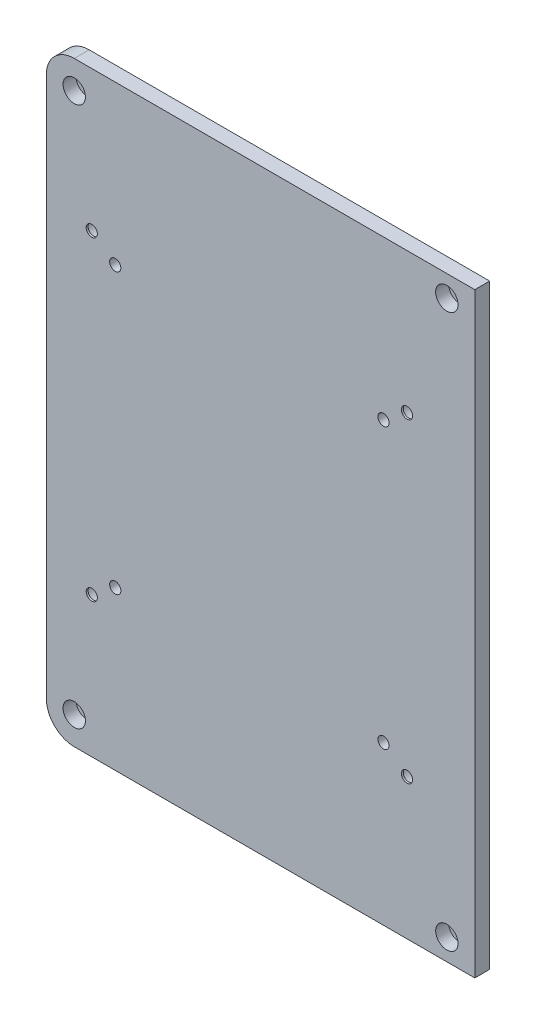
SolidWorks part; units mm, degrees
ref_plane "Front Plane" through (0, 0, 0) normal (0, 0, 1) x (1, 0, 0)
ref_plane "Top Plane" through (0, 0, 0) normal (0, 1, 0) x (1, 0, 0)
ref_plane "Right Plane" through (0, 0, 0) normal (1, 0, 0) x (0, 0, -1)
sketch "Sketch1" plane through (0, 0, 0) normal (0, 0, 1) x (1, 0, 0)
  line L1 (-107.5, 80) -> (107.5, 80)
  line L2 (-115, 72.5) -> (-115, -72.5)
  line L3 (-107.5, -80) -> (107.5, -80)
  line L4 (115, 72.5) -> (115, -72.5)
  line L5 (-115, 80) -> (115, -80) construction
  line L6 (-115, -80) -> (115, 80) construction
  arc A0 (-115, -72.5) -> (-107.5, -80) centre (-107.5, -72.5) ccw
  arc A1 (107.5, -80) -> (115, -72.5) centre (107.5, -72.5) ccw
  arc A2 (107.5, 80) -> (115, 72.5) centre (107.5, 72.5) cw
  arc A3 (-107.5, 80) -> (-115, 72.5) centre (-107.5, 72.5) ccw
  point P0 (0, 0)
  dimension "D3" = 7.5
  dimension "D1" = 230
  dimension "D2" = 160
extrude "Boss-Extrude1" add sketch "Sketch1" along normal blind 4
sketch "Sketch2" plane through (0, 0, 4) normal (0, 0, 1) x (1, 0, 0)
  line L0 (-115, 72.5) -> (-115, -72.5) construction
  line L1 (-107.5, -80) -> (107.5, -80) construction
  line L2 (107.5, 80) -> (-107.5, 80) construction
  line L3 (115, -72.5) -> (115, 72.5) construction
  circle A0 centre (-107.5, -72.5) radius 1.75
  circle A1 centre (-107.5, 72.5) radius 1.75
  circle A2 centre (107.5, -72.5) radius 1.75
  circle A3 centre (107.5, 72.5) radius 1.75
  dimension "D1" = 7.5
  dimension "D3" = 3.5
  dimension "D4" = 3.5
  dimension "D7" = 3.5
  dimension "D10" = 3.5
  dimension "D2" = 7.5
  dimension "D5" = 7.5
  dimension "D6" = 7.5
  dimension "D8" = 7.5
  dimension "D9" = 7.5
  dimension "D11" = 7.5
  dimension "D12" = 7.5
extrude "Cut-Extrude1" cut sketch "Sketch2" against normal blind 10
sketch "Sketch3" plane through (0, 0, 4) normal (0, 0, 1) x (1, 0, 0)
  circle A0 centre (-107.5, -72.5) radius 3
  circle A1 centre (-107.5, 72.5) radius 3
  circle A2 centre (107.5, 72.5) radius 3
  circle A3 centre (107.5, -72.5) radius 3
  dimension "D1" = 6
  dimension "D2" = 6
  dimension "D3" = 6
  dimension "D4" = 6
extrude "Cut-Extrude2" cut sketch "Sketch3" against normal blind 3.5
sketch "Sketch4" plane through (0, 0, 4) normal (0, 0, 1) x (1, 0, 0)
  line L0 (107.5, 80) -> (-107.5, 80) construction
  line L3 (-115, 72.5) -> (-115, -72.5) construction
  line L4 (-107.5, -80) -> (107.5, -80) construction
  circle A0 centre (-96.5, 37.5) radius 1.5
  circle A1 centre (-96.5, -37.5) radius 1.5
  circle A2 centre (-24.5, 37.5) radius 1.5
  circle A3 centre (-24.5, -37.5) radius 1.5
  dimension "D2" = 3
  dimension "D3" = 3
  dimension "D6" = 3
  dimension "D7" = 3
  dimension "D1" = 75
  dimension "D4" = 42.5
  dimension "D5" = 18.5
  dimension "D8" = 72
  dimension "D9" = 72
  dimension "D10" = 42.5
  dimension "D11" = 42.5
extrude "Cut-Extrude3" cut sketch "Sketch4" against normal through all
sketch "Sketch5" plane through (0, 0, 4) normal (0, 0, 1) x (1, 0, 0)
  line L0 (-107.5, -80) -> (107.5, -80) construction
  line L2 (115, -72.5) -> (115, 72.5) construction
  circle A0 centre (95, -62.5) radius 1.375
  circle A1 centre (95, 62.5) radius 1.375
  circle A2 centre (41.7, -62.5) radius 1.375
  circle A3 centre (41.7, 62.5) radius 1.375
  dimension "D1" = 125
  dimension "D4" = 2.75
  dimension "D6" = 53.3
  dimension "D2" = 17.5
  dimension "D3" = 20
  dimension "D5" = 53.3
extrude "Cut-Extrude4" cut sketch "Sketch5" against normal through all and the other way through all
sketch "Sketch7" plane through (0, 0, 4) normal (0, 0, 1) x (1, 0, 0)
  circle A0 centre (-102.8, 42.3) radius 1.5
  circle A1 centre (-96.5, 37.5) radius 1.5 construction
  circle A2 centre (-102.8, -42.3) radius 1.5
  circle A3 centre (-18.2, -42.3) radius 1.5
  circle A4 centre (-18.2, 42.3) radius 1.5
  circle A5 centre (-96.5, -37.5) radius 1.5 construction
  circle A6 centre (-24.5, -37.5) radius 1.5 construction
  circle A7 centre (-24.5, 37.5) radius 1.5 construction
  dimension "D1" = 6.3
  dimension "D3" = 3
  dimension "D4" = 3
  dimension "D5" = 3
  dimension "D6" = 3
  dimension "D7" = 4.8
  dimension "D8" = 6.3
  dimension "D10" = 4.8
  dimension "D11" = 4.8
  dimension "D12" = 6.3
  dimension "D2" = 4.8
extrude "Cut-Extrude6" cut sketch "Sketch7" against normal through all
sketch "Sketch8" plane through (0, 0, 0) normal (0, 0, -1) x (-1, 0, 0)
  circle A0 centre (18.2, 42.3) radius 3
  circle A1 centre (18.2, -42.3) radius 3
  circle A2 centre (102.8, -42.3) radius 3
  circle A3 centre (102.8, 42.3) radius 3
  dimension "D1" = 6
  dimension "D2" = 6
  dimension "D3" = 6
  dimension "D4" = 6
extrude "Cut-Extrude7" cut sketch "Sketch8" against normal blind 3.5
sketch "Sketch9" plane through (0, 0, 4) normal (0, 0, 1) x (1, 0, 0)
  line L0 (115, -72.5) -> (115, 72.5) construction
  line L1 (0, 80) -> (115, 80)
  line L2 (0, 80) -> (0, -80)
  line L3 (0, -80) -> (115, -80)
  line L4 (115, 80) -> (115, -80)
  line L5 (107.5, 80) -> (-107.5, 80) construction
  line L6 (-107.5, -80) -> (107.5, -80) construction
  line L7 (-115, 72.5) -> (-115, -72.5) construction
  dimension "D1" = 0
  dimension "D2" = 0
  dimension "D3" = 0
  dimension "D4" = 115
extrude "Cut-Extrude8" cut sketch "Sketch9" against normal blind 10
sketch "Sketch10" plane through (0, 0, 4) normal (0, 0, 1) x (1, 0, 0)
  line L0 (0, 80) -> (0, -80) construction
  line L1 (-107.5, -80) -> (0, -80) construction
  circle A0 centre (-7.5, -74.25) radius 1.75
  dimension "D1" = 3.5
  dimension "D2" = 7.5
  dimension "D3" = 5.75
extrude "Cut-Extrude9" cut sketch "Sketch10" against normal up to surface (4 mm away) up to face at (-21.2, -42.3, 0)
sketch "Sketch14" plane through (0, 0, 4) normal (0, 0, 1) x (1, 0, 0)
  line L0 (0, 80) -> (0, -80) construction
  line L1 (-107.5, -80) -> (0, -80) construction
  circle A0 centre (-7.5, -74.25) radius 3
  dimension "D3" = 6
  dimension "D1" = 7.5
  dimension "D2" = 5.75
extrude "Cut-Extrude10" cut sketch "Sketch14" against normal blind 3.5
sketch "Sketch16" plane through (0, 0, 4) normal (0, 0, 1) x (1, 0, 0)
  line L0 (0, 80) -> (-107.5, 80) construction
  line L1 (0, 80) -> (0, -80) construction
  circle A0 centre (-7.5, 74.25) radius 1.75
  dimension "D3" = 3.5
  dimension "D1" = 5.75
  dimension "D2" = 7.5
extrude "Cut-Extrude11" cut sketch "Sketch16" against normal up to surface (4 mm away) up to face at (-5.75, -74.25, 0)
sketch "Sketch17" plane through (0, 0, 4) normal (0, 0, 1) x (1, 0, 0)
  line L0 (0, 80) -> (-107.5, 80) construction
  line L1 (0, 80) -> (0, -80) construction
  circle A0 centre (-7.5, 74.25) radius 3
  dimension "D1" = 6
  dimension "D2" = 5.75
  dimension "D3" = 7.5
extrude "Cut-Extrude12" cut sketch "Sketch17" against normal blind 3.5
